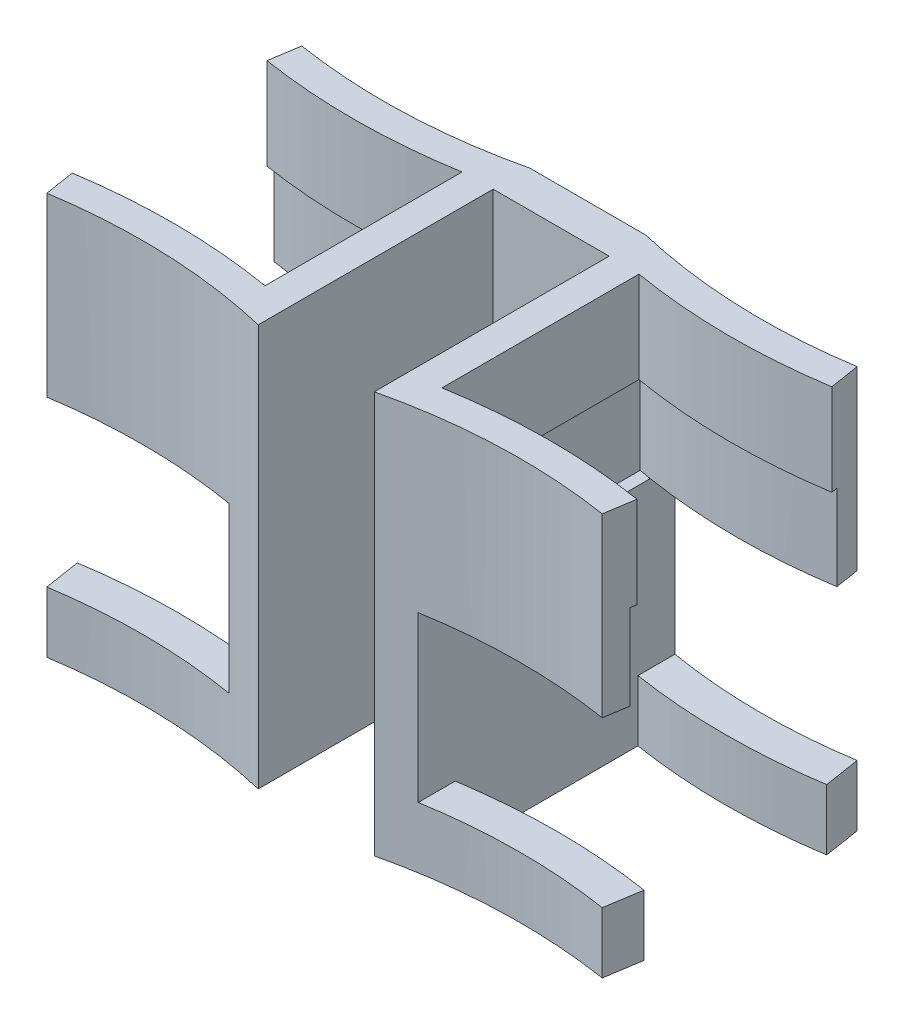
SolidWorks part; units mm, degrees
ref_plane "Front Plane" through (0, 0, 0) normal (0, 0, 1) x (1, 0, 0)
ref_plane "Top Plane" through (0, 0, 0) normal (0, 1, 0) x (1, 0, 0)
ref_plane "Right Plane" through (0, 0, 0) normal (1, 0, 0) x (0, 0, -1)
sketch "Sketch1" plane through (0, 0, 0) normal (0, 1, 0) x (1, 0, 0)
  line L0 (-6, -1.2833) -> (-6, -31.2833)
  line L1 (0, 0) -> (0, -38.5665)
  line L2 (-37, -1.2833) -> (-36.07, 4.6442)
  line L3 (-37, -31.2833) -> (-36.07, -37.2107)
  line L4 (0, 6) -> (19.05, 6)
  line L5 (25.05, -1.2833) -> (25.05, -31.2833)
  line L6 (19.05, 0) -> (19.05, -38.5665)
  line L7 (56.05, -1.2833) -> (55.12, 4.6442)
  line L8 (56.05, -31.2833) -> (55.12, -37.2107)
  line L9 (0, 0) -> (19.05, 0)
  line L10 (0, 6) -> (0, -38.5665) construction
  line L11 (19.05, 6) -> (19.05, -38.5665) construction
  arc A0 (-6, -1.2833) -> (-37, -1.2833) centre (-21.5, 97.5082) cw
  arc A1 (-6, -31.2833) -> (-37, -31.2833) centre (-21.5, -130.0747) ccw
  arc A2 (0, 6) -> (-36.07, 4.6442) centre (-21.5, 97.5082) cw
  arc A3 (0, -38.5665) -> (-36.07, -37.2107) centre (-21.5, -130.0747) ccw
  arc A4 (25.05, -1.2833) -> (56.05, -1.2833) centre (40.55, 97.5082) ccw
  arc A5 (25.05, -31.2833) -> (56.05, -31.2833) centre (40.55, -130.0747) cw
  arc A6 (19.05, 6) -> (55.12, 4.6442) centre (40.55, 97.5082) ccw
  arc A7 (19.05, -38.5665) -> (55.12, -37.2107) centre (40.55, -130.0747) cw
  point P20 (0, 0)
  dimension "D1" = 100
  dimension "D2" = 31
  dimension "D3" = 30
  dimension "D4" = 31
  dimension "D5" = 31
  dimension "D7" = 31
  dimension "D9" = 30
  dimension "D10" = 19.05
  dimension "D11" = 6
  dimension "D6" = 6
  dimension "D8" = 6
extrude "Boss-Extrude1" add sketch "Sketch1" along normal blind 66
sketch "Sketch2" plane through (0, 66, 0) normal (0, 1, 0) x (1, 0, 0)
  line L12 (-6, -1.2833) -> (-6, -31.2833)
  line L13 (25.05, -1.2833) -> (25.05, -31.2833)
  line L14 (56.05, -1.2833) -> (56.05, -31.2833)
  line L15 (-37, -1.2833) -> (-37, -31.2833)
  line L16 (-5, -0.1071) -> (-5, -32.4594)
  line L17 (-38, -0.1071) -> (-38, -32.4594)
  line L18 (57.05, -0.1071) -> (57.05, -32.4594)
  line L19 (24.05, -0.1071) -> (24.05, -32.4594)
  arc A24 (-37, -1.2833) -> (-6, -1.2833) centre (-21.5, 97.5082) ccw
  arc A25 (-37, -31.2833) -> (-6, -31.2833) centre (-21.5, -130.0747) cw
  arc A26 (25.05, -1.2833) -> (56.05, -1.2833) centre (40.55, 97.5082) ccw
  arc A27 (25.05, -31.2833) -> (56.05, -31.2833) centre (40.55, -130.0747) cw
  arc A28 (56.05, -31.2833) -> (25.05, -31.2833) centre (40.55, -130.0747) ccw construction
  arc A29 (-38, -0.1071) -> (-5, -0.1071) centre (-21.5, 97.5082) ccw
  arc A30 (-38, -32.4594) -> (-5, -32.4594) centre (-21.5, -130.0747) cw
  arc A31 (24.05, -32.4594) -> (57.05, -32.4594) centre (40.55, -130.0747) cw
  arc A32 (24.05, -0.1071) -> (57.05, -0.1071) centre (40.55, 97.5082) ccw
  dimension "D1" = 100
  dimension "D2" = 1
  dimension "D3" = 1
extrude "Cut-Extrude1" cut sketch "Sketch2" against normal blind 15
sketch "Sketch3" plane through (0, 51, 0) normal (0, 1, 0) x (1, 0, 0)
  line L0 (-37, -1.2833) -> (-37, -31.2833)
  line L1 (-6, -1.2833) -> (-6, -31.2833)
  line L2 (25.05, -1.2833) -> (25.05, -31.2833)
  line L3 (56.05, -1.2833) -> (56.05, -31.2833)
  line L4 (-4, 1.0834) -> (-4, -33.6499)
  line L5 (-39, 1.0834) -> (-39, -33.6499)
  line L6 (58.05, 1.0834) -> (58.05, -33.6499)
  line L7 (23.05, 1.0834) -> (23.05, -33.6499)
  arc A0 (-37, -1.2833) -> (-6, -1.2833) centre (-21.5, 97.5082) ccw
  arc A1 (-37, -31.2833) -> (-6, -31.2833) centre (-21.5, -130.0747) cw
  arc A2 (25.05, -1.2833) -> (56.05, -1.2833) centre (40.55, 97.5082) ccw
  arc A3 (25.05, -31.2833) -> (56.05, -31.2833) centre (40.55, -130.0747) cw
  arc A4 (-39, -33.6499) -> (-4, -33.6499) centre (-21.5, -130.0747) cw
  arc A5 (-39, 1.0834) -> (-4, 1.0834) centre (-21.5, 97.5082) ccw
  arc A6 (23.05, -33.6499) -> (58.05, -33.6499) centre (40.55, -130.0747) cw
  arc A7 (23.05, 1.0834) -> (58.05, 1.0834) centre (40.55, 97.5082) ccw
  dimension "D1" = 100
  dimension "D2" = 2
extrude "Cut-Extrude2" cut sketch "Sketch3" against normal blind 14
sketch "Sketch4" plane through (-6, 0, 0) normal (-1, 0, 0) x (0, 0, 1)
  line L0 (-6, 37) -> (38.5665, 37)
  line L1 (31.2833, 37) -> (1.2833, 37) construction
  line L2 (38.5665, 37) -> (38.5665, 10)
  line L3 (38.5665, 10) -> (-6, 10)
  line L4 (-6, 10) -> (-6, 37)
  line L5 (-6, 66) -> (-6, 0) construction
  line L6 (38.5665, 66) -> (38.5665, 0) construction
  line L7 (1.2833, 0) -> (31.2833, 0) construction
  point P6 (0, 0)
  point P9 (0, 0)
  point P10 (0, 0)
  dimension "D1" = 10
extrude "Cut-Extrude3" cut sketch "Sketch4" along normal through all
sketch "Sketch5" plane through (25.05, 0, 0) normal (1, 0, 0) x (0, 0, -1)
  line L0 (-38.5665, 37) -> (6, 37)
  line L1 (6, 37) -> (6, 10)
  line L2 (6, 10) -> (-38.5665, 10)
  line L3 (-38.5665, 10) -> (-38.5665, 37)
  line L4 (-1.2833, 37) -> (-31.2833, 37) construction
  line L5 (-38.5665, 66) -> (-38.5665, 0) construction
  line L6 (6, 66) -> (6, 0) construction
  line L7 (-31.2833, 0) -> (-1.2833, 0) construction
  point P6 (0, 0)
  point P11 (0, 0)
  dimension "D1" = 10
extrude "Cut-Extrude4" cut sketch "Sketch5" along normal through all
